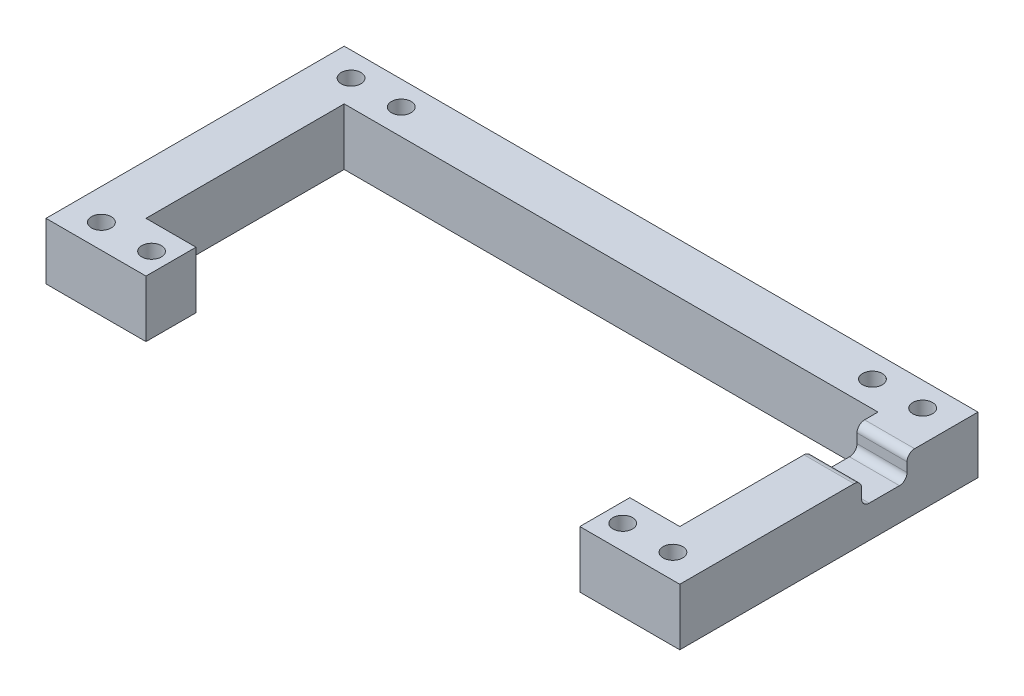
SolidWorks part; units mm, degrees
ref_plane "Front Plane" through (0, 0, 0) normal (0, 0, 1) x (1, 0, 0)
ref_plane "Top Plane" through (0, 0, 0) normal (0, 1, 0) x (1, 0, 0)
ref_plane "Right Plane" through (0, 0, 0) normal (1, 0, 0) x (0, 0, -1)
sketch "Sketch1" plane through (0, 0, 0) normal (0, 1, 0) x (1, 0, 0)
  line L0 (181.4198, 36.9979) -> (75.1552, 36.9979) construction
  line L1 (75.1552, 11.9979) -> (83.5372, 11.9979)
  line L2 (75.1552, 11.9979) -> (75.1552, 61.9979)
  line L3 (75.1552, 61.9979) -> (83.5372, 61.9979)
  line L4 (83.5372, 11.9979) -> (83.5372, 61.9979)
  line L5 (83.5372, 61.9979) -> (91.9192, 61.9979)
  line L6 (83.5372, 61.9979) -> (83.5372, 53.6159)
  line L7 (83.5372, 53.6159) -> (91.9192, 53.6159)
  line L8 (167.7876, 16.0648) -> (186.7138, 16.0648) construction
  line L9 (83.5372, 11.9979) -> (91.9192, 11.9979)
  line L10 (83.5372, 11.9979) -> (83.5372, 20.3799)
  line L11 (83.5372, 20.3799) -> (91.9192, 20.3799)
  line L12 (91.9192, 11.9979) -> (91.9192, 20.3799)
  line L13 (75.1552, 61.9979) -> (181.4198, 61.9979)
  line L17 (181.4198, 61.9979) -> (173.0378, 61.9979)
  line L18 (181.4198, 61.9979) -> (181.4198, 11.9979)
  line L19 (181.4198, 11.9979) -> (173.0378, 11.9979)
  line L20 (173.0378, 61.9979) -> (173.0378, 11.9979)
  line L21 (173.0378, 61.9979) -> (164.6558, 61.9979)
  line L22 (173.0378, 61.9979) -> (173.0378, 53.6159)
  line L23 (173.0378, 53.6159) -> (164.6558, 53.6159)
  line L25 (173.0378, 11.9979) -> (164.6558, 11.9979)
  line L26 (173.0378, 11.9979) -> (173.0378, 20.3799)
  line L27 (173.0378, 20.3799) -> (164.6558, 20.3799)
  line L28 (164.6558, 11.9979) -> (164.6558, 20.3799)
  line L29 (128.2875, 61.9979) -> (128.2875, -9.1774) construction
  line L30 (164.6558, 53.6159) -> (91.9192, 53.6159)
  circle A0 centre (167.7876, 57.931) radius 1.651
  circle A1 centre (167.7876, 16.0648) radius 1.651
  circle A2 centre (88.7875, 16.0648) radius 1.651
  circle A3 centre (88.7875, 57.931) radius 1.651
  circle A4 centre (176.2028, 16.0648) radius 1.651
  circle A5 centre (80.3722, 16.0648) radius 1.651
  circle A6 centre (80.3722, 57.931) radius 1.651
  circle A7 centre (176.2028, 57.931) radius 1.651
  point P32 (91.9192, 16.1889)
  point P34 (88.7875, 57.931)
  point P35 (88.7875, 16.0648)
  dimension "D15" = 3.302
  dimension "D16" = 3.1342
  dimension "D6" = 79.0001
  dimension "D18" = 3.302
  dimension "D2" = 47.9153
  dimension "D1" = 8.382
  dimension "D3" = 50
  dimension "D4" = 8.382
  dimension "D5" = 50
  dimension "D7" = 8.382
  dimension "D8" = 8.382
  dimension "D9" = 8.382
  dimension "D10" = 8.382
  dimension "D11" = 8.382
  dimension "D12" = 8.382
  dimension "D13" = 8.382
  dimension "D14" = 8.382
  dimension "D17" = 3.1317
extrude "Boss-Extrude1" add sketch "Sketch1" along normal blind 9.525 contours L1 L4 L3 L2 | L13 L3 L5 | L13 L20 L19 L18 | L13 L23 L20 | L28 L25 L20 L27 | L9 L12 L11 L4 | L5 L4 L7 | L1 L4 L2 | L20 L19 L18 region at (79.3025, 0, -36.9979) region at (83.6557, 0, -16.1889) region at (128.2875, 0, -57.804) region at (177.2725, 0, -36.9979) region at (172.9193, 0, -16.1889)
sketch "Sketch2" plane through (181.4198, 0, 0) normal (1, 0, 0) x (0, 0, -1)
  line L0 (61.9979, 9.525) -> (11.9979, 9.525) construction
  line L1 (42.4779, 9.525) -> (50.0979, 9.525)
  line L2 (42.4779, 9.525) -> (42.4779, 5.4254)
  line L3 (42.4779, 5.4254) -> (50.0979, 5.4254)
  line L4 (50.0979, 9.525) -> (50.0979, 5.4254)
  line L5 (11.9979, 9.525) -> (11.9979, 0) construction
  dimension "D1" = 30.48
  dimension "D2" = 7.62
extrude "Cut-Extrude7" cut sketch "Sketch2" against normal blind 8.89 contours L2 L3 L4 L1
fillet "Fillet2" radius 1.27 4 edges at (177.2288, 5.4254, -42.4779) (177.2288, 9.525, -42.4779) (177.2288, 9.525, -50.0979) (177.2288, 5.4254, -50.0979)
